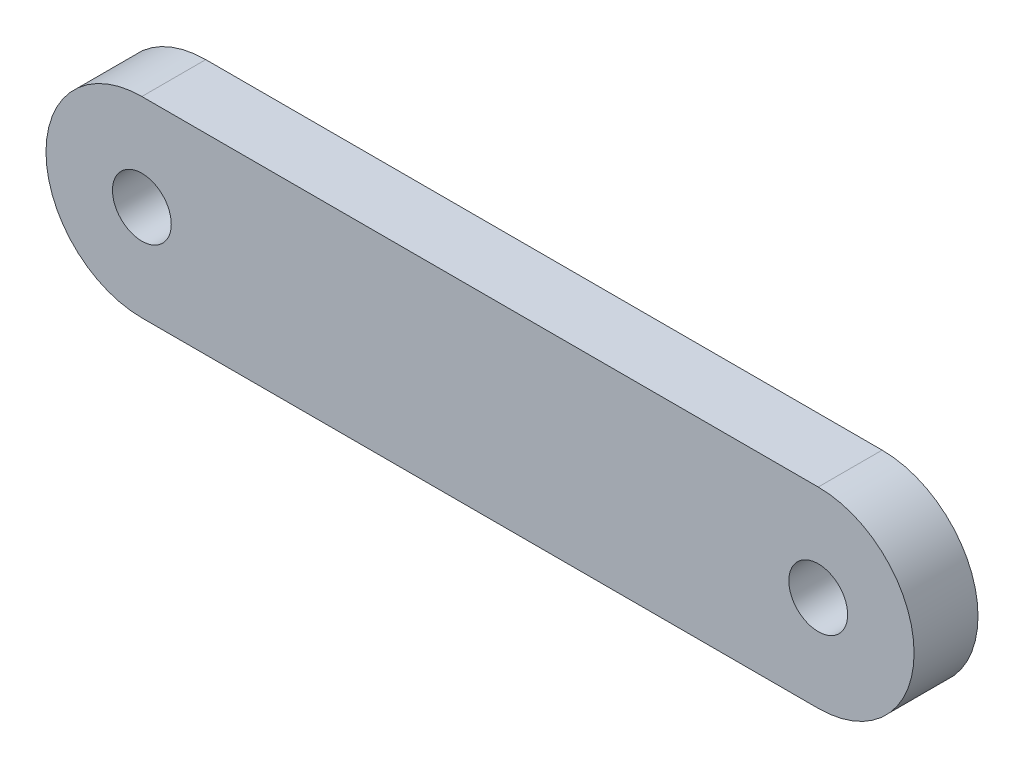
SolidWorks part; units mm, degrees
ref_plane "前视基准面" through (0, 0, 0) normal (0, 0, 1) x (1, 0, 0)
ref_plane "上视基准面" through (0, 0, 0) normal (0, 1, 0) x (1, 0, 0)
ref_plane "右视基准面" through (0, 0, 0) normal (1, 0, 0) x (0, 0, -1)
other "Configuration Table"
sketch "草图1" plane through (0, 0, 0) normal (0, 0, 1) x (1, 0, 0)
  line L1 (-26.46, 7.5) -> (26.46, 7.5)
  line L3 (-26.46, -7.5) -> (26.46, -7.5)
  line L5 (-26.46, 7.5) -> (26.46, -7.5) construction
  line L6 (-26.46, -7.5) -> (26.46, 7.5) construction
  arc A0 (-26.46, 7.5) -> (-26.46, -7.5) centre (-26.46, 0) ccw
  arc A1 (26.46, 7.5) -> (26.46, -7.5) centre (26.46, 0) cw
  circle A2 centre (-26.46, 0) radius 2.3
  circle A3 centre (26.46, 0) radius 2.3
  point P0 (0, 0)
  dimension "D1" = 4.6
  dimension "D2" = 4.6
  dimension "D3" = 52.92
  dimension "D4" = 15
extrude "凸台-拉伸1" add sketch "草图1" along normal blind 5
equation "\"fi\"=4.6"
equation "\"D1@草图1\"=\"fi\""
equation "\"D2@草图1\"=\"fi\""
equation "\"b0\"= 75.6'ground"
equation "\"b1\"= \"b0\" *1.4/ 2'rocker"
equation "\"D3@草图1\"=\"b1\""
equation "\"width\"=15"
equation "\"D4@草图1\"=\"width\""
equation "\"depth\"=5"
equation "\"D1@凸台-拉伸1\"=\"depth\""
equation "\"b2\"= \"b0\"'coupler"
equation "\"b3\"= \"b0\" / 2'coupler"
equation "\"b4\"= \"b0\" *2'leg"
equation "\"angle\"= 90度'左右cranker夹角"
